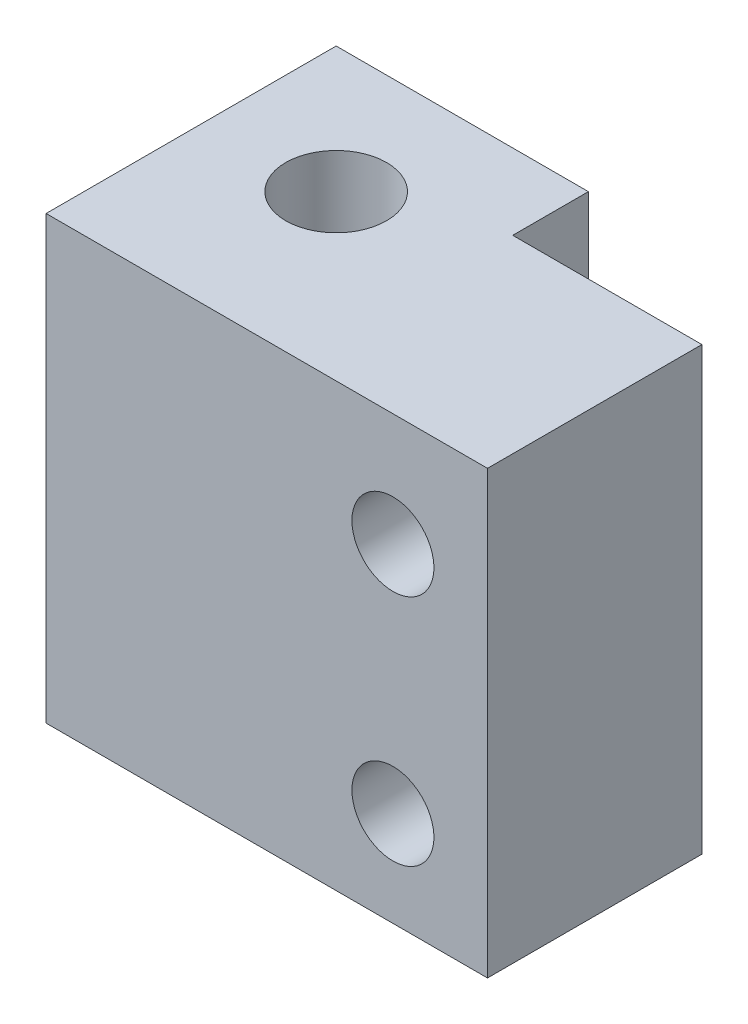
SolidWorks part; units mm, degrees
ref_plane "Front Plane" through (0, 0, 0) normal (0, 0, 1) x (1, 0, 0)
ref_plane "Top Plane" through (0, 0, 0) normal (0, 1, 0) x (1, 0, 0)
ref_plane "Right Plane" through (0, 0, 0) normal (1, 0, 0) x (0, 0, -1)
sketch "Sketch1" plane through (0, 0, 0) normal (0, 1, 0) x (1, 0, 0)
  line L5 (-10, -5.2575) -> (-10, 0.7425)
  line L6 (-10, 0.7425) -> (10, 0.7425)
  line L9 (25, -5.2575) -> (25, -22.2575)
  line L10 (0, -22.2575) -> (0, 0.7425) construction
  line L11 (-10, -5.2575) -> (-10, -22.2575)
  line L12 (10, 0.7425) -> (10, -5.2575)
  line L13 (10, -5.2575) -> (25, -5.2575)
  line L14 (-10, -22.2575) -> (25, -22.2575)
  point P2 (0, 0)
  dimension "D5" = 17
  dimension "D6" = 15
extrude "Boss-Extrude2" add sketch "Sketch1" along normal blind 35
sketch "Sketch3" plane through (0, 0, 0) normal (0, -1, 0) x (1, 0, 0)
  line L0 (0, -0.7425) -> (0, 22.2575) construction
  line L1 (10, -0.7425) -> (-10, -0.7425) construction
  circle A0 centre (0, 9.2575) radius 4
  dimension "D1" = 8
  dimension "D2" = 10
extrude "Cut-Extrude1" cut sketch "Sketch3" against normal up to next
sketch "Sketch4" plane through (0, 0, 5.2575) normal (0, 0, -1) x (-1, 0, 0)
  line L0 (-25, 17.5) -> (-10, 17.5) construction
  line L1 (-25, 35) -> (-25, 0) construction
  line L2 (-10, 35) -> (-10, 0) construction
  line L3 (-17.5, 35) -> (-17.5, 0) construction
  line L4 (-25, 35) -> (-10, 35) construction
  line L5 (-25, 0) -> (-10, 0) construction
  circle A0 centre (-17.5, 26.0458) radius 3.25
  circle A2 centre (-17.5, 7.5353) radius 3.25
  dimension "D1" = 6.5
  dimension "D2" = 6.5
extrude "Cut-Extrude2" cut sketch "Sketch4" against normal up to next
sketch "Sketch5" plane through (0, 0, 0) normal (0, -1, 0) x (1, 0, 0)
  line L0 (0, -0.7425) -> (0, 22.2575) construction
  line L1 (10, -0.7425) -> (-10, -0.7425) construction
  line L2 (-10, 22.2575) -> (25, 22.2575) construction
